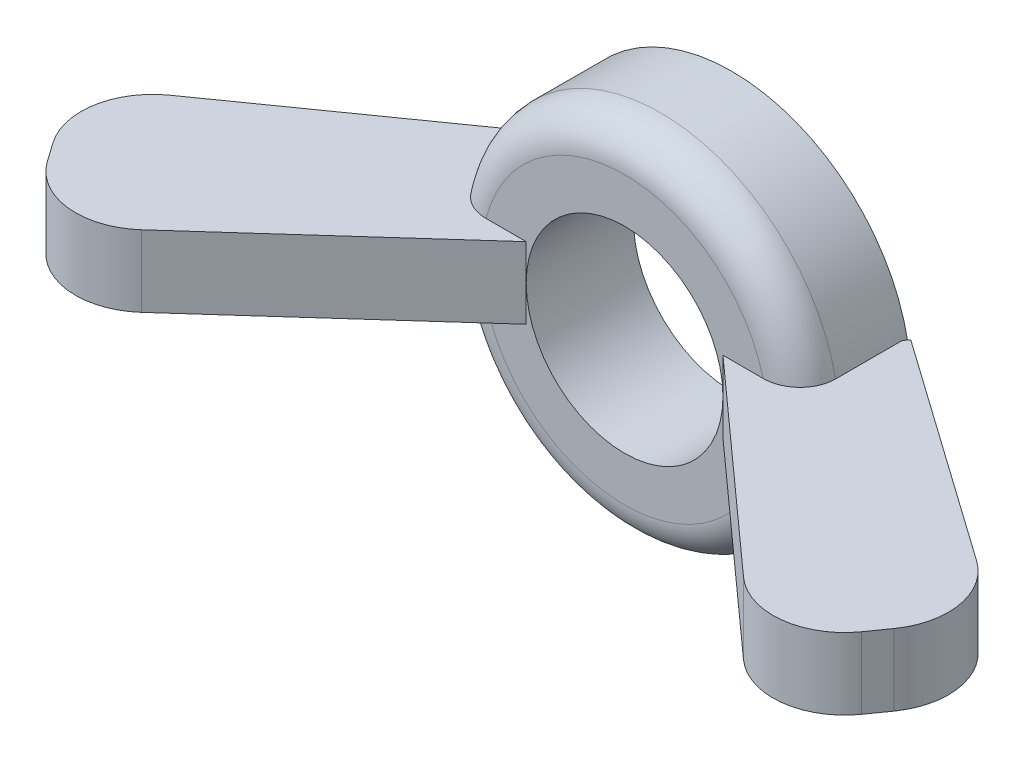
SolidWorks part; units mm, degrees
ref_plane "Plan de face" through (0, 0, 0) normal (0, 0, 1) x (1, 0, 0)
ref_plane "Plan de dessus" through (0, 0, 0) normal (0, 1, 0) x (1, 0, 0)
ref_plane "Plan de droite" through (0, 0, 0) normal (1, 0, 0) x (0, 0, -1)
sketch "Esquisse1" plane through (0, 0, 0) normal (0, 0, 1) x (1, 0, 0)
  circle A0 centre (0, 0) radius 2.75
  circle A1 centre (0, 0) radius 5
  dimension "D1" = 5.5
  dimension "D2" = 10
extrude "Boss.-Extru.1" add sketch "Esquisse1" along normal blind 3
sketch "Esquisse2" plane through (0, 0, 0) normal (0, 1, 0) x (1, 0, 0)
  line L0 (-5, 0) -> (-11.2783, -4.436)
  line L1 (-11.7576, -7.2235) -> (-11.3829, -7.7538)
  line L2 (-5, 0) -> (-2.75, -3)
  line L3 (-8.4129, -8.0875) -> (-2.75, -3)
  line L4 (0, 0) -> (0, -8.0319) construction
  line L5 (8.4129, -8.0875) -> (2.75, -3)
  line L6 (5, 0) -> (2.75, -3)
  line L7 (11.7576, -7.2235) -> (11.3829, -7.7538)
  line L8 (5, 0) -> (11.2783, -4.436)
  arc A0 (-11.2783, -4.436) -> (-11.7576, -7.2235) centre (-10.1242, -6.0694) ccw
  arc A1 (-11.3829, -7.7538) -> (-8.4129, -8.0875) centre (-9.7495, -6.5997) ccw
  arc A2 (11.3829, -7.7538) -> (8.4129, -8.0875) centre (9.7495, -6.5997) cw
  arc A3 (11.2783, -4.436) -> (11.7576, -7.2235) centre (10.1242, -6.0694) cw
  point P8 (-12.9117, -5.5901)
  point P11 (-10.0855, -9.5901)
  point P23 (10.0855, -9.5901)
  point P24 (12.9117, -5.5901)
  dimension "D2" = 2
  dimension "D1" = 4
extrude "Boss.-Extru.2" add sketch "Esquisse2" along normal blind 1 and the other way blind 1
fillet "Congé1" radius 1 2 edges at (0, 5, 3) (0, -5, 3)
